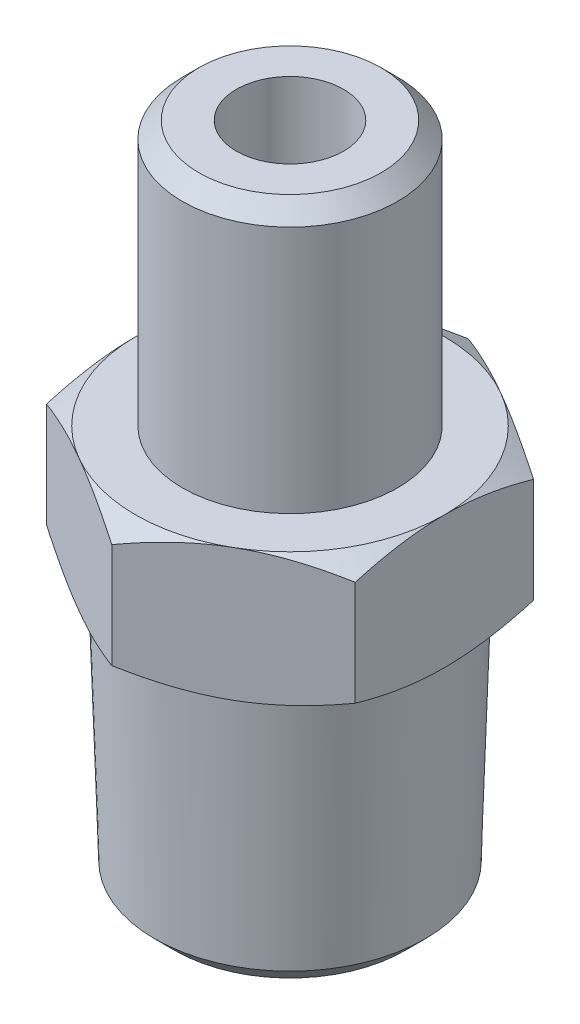
SolidWorks part; units mm, degrees
ref_plane "Front Plane" through (0, 0, 0) normal (0, 0, 1) x (1, 0, 0)
ref_plane "Top Plane" through (0, 0, 0) normal (0, 1, 0) x (1, 0, 0)
ref_plane "Right Plane" through (0, 0, 0) normal (1, 0, 0) x (0, 0, -1)
sketch "Sketch1" plane through (0, 0, 0) normal (0, 0, 1) x (1, 0, 0)
  line L0 (0, 0) -> (0, 23.8125) construction
  point P3 (0, 14.2875)
  point P4 (0, 9.525)
  dimension "Overall Length" = 23.8125
  dimension "Outlet Length" = 9.525
  dimension "Inlet Length" = 9.525
sketch "Sketch6" plane through (0, 0, 0) normal (0, 1, 0) x (1, 0, 0)
  line L1 (5.5562, -3.2079) -> (5.5562, 3.2079)
  line L2 (5.5562, 3.2079) -> (0, 6.4158)
  line L3 (0, 6.4158) -> (-5.5563, 3.2079)
  line L4 (-5.5563, 3.2079) -> (-5.5563, -3.2079)
  line L5 (-5.5563, -3.2079) -> (0, -6.4158)
  line L6 (0, -6.4158) -> (5.5562, -3.2079)
  circle A0 centre (0, 0) radius 5.5562 construction
  circle A1 centre (0, 0) radius 5.1435
  circle A2 centre (0, 0) radius 3.8735
ref_plane "Plane1" through (0, 23.8125, 0) normal (0, 1, 0) x (1, 0, 0)
ref_plane "Plane2" through (0, 9.525, 0) normal (0, 1, 0) x (1, 0, 0)
sketch "Sketch7" plane through (0, 9.525, 0) normal (0, 1, 0) x (1, 0, 0)
  circle A0 centre (0, 0) radius 5.1435 construction
  circle A1 centre (0, 0) radius 5.1435
extrude "Boss-Extrude3" add sketch "Sketch7" against normal up to vertex (9.525 mm away) draft 1.783 up to point (0, 0, 0)
sketch "Sketch8" plane through (0, 9.525, 0) normal (0, 1, 0) x (1, 0, 0)
  line L0 (5.5562, -3.2079) -> (5.5562, 3.2079) construction
  line L1 (5.5562, 3.2079) -> (0, 6.4158) construction
  line L2 (0, 6.4158) -> (-5.5563, 3.2079) construction
  line L3 (-5.5563, 3.2079) -> (-5.5563, -3.2079) construction
  line L4 (-5.5563, -3.2079) -> (0, -6.4158) construction
  line L5 (0, -6.4158) -> (5.5562, -3.2079) construction
  line L6 (5.5562, -3.2079) -> (5.5562, 3.2079)
  line L7 (5.5562, 3.2079) -> (0, 6.4158)
  line L8 (0, 6.4158) -> (-5.5563, 3.2079)
  line L9 (-5.5563, 3.2079) -> (-5.5563, -3.2079)
  line L10 (-5.5563, -3.2079) -> (0, -6.4158)
  line L11 (0, -6.4158) -> (5.5562, -3.2079)
extrude "Boss-Extrude4" add sketch "Sketch8" along normal up to vertex (4.7625 mm away) up to point (0, 14.2875, 0)
sketch "Sketch9" plane through (0, 23.8125, 0) normal (0, 1, 0) x (1, 0, 0)
  circle A0 centre (0, 0) radius 3.8735 construction
  circle A1 centre (0, 0) radius 3.8735
extrude "Boss-Extrude5" add sketch "Sketch9" against normal up to vertex (9.525 mm away) up to point (0, 14.2875, 0)
ref_plane "Plane3" through (0, 11.9062, 0) normal (0, 1, 0) x (1, 0, 0)
sketch "Sketch10" plane through (0, 0, 0) normal (0, 1, 0) x (1, 0, 0)
  circle A0 centre (0, 0) radius 1.9304
  dimension "D1" = 3.8608
extrude "Cut-Extrude1" cut sketch "Sketch10" along normal through all
sketch "Sketch11" plane through (0, 9.525, 0) normal (0, 1, 0) x (1, 0, 0)
  circle A2 centre (0, 0) radius 5.5562 construction
  circle A3 centre (0, 0) radius 5.5562
extrude "Cut-Extrude2" cut sketch "Sketch11" along normal through all draft 60 flip side to cut
mirror "Mirror1" about plane through (0, 11.9062, 0) normal (0, 1, 0) of "Cut-Extrude2"
sketch "Sketch12" plane through (0, 0, 0) normal (0, 0, 1) x (1, 0, 0)
  line L2 (4.5212, 16.8148) -> (4.5212, 20.4292)
  line L3 (4.5212, 20.4292) -> (4.1656, 20.7848)
  line L4 (4.1656, 20.7848) -> (4.1656, 23.4594)
  line L5 (4.1656, 23.4594) -> (4.5212, 23.8125)
  line L6 (4.5212, 23.8125) -> (4.5212, 27.9832)
  line L7 (4.5212, 27.9832) -> (3.085, 27.9832)
  line L11 (6.1119, 23.8125) -> (-6.1119, 23.8125) construction
  line L12 (4.0259, 23.8125) -> (3.6703, 23.4594)
  line L13 (3.6703, 23.4594) -> (3.6703, 20.7848)
  line L14 (3.6703, 20.7848) -> (4.0259, 20.4292)
  line L15 (4.0259, 20.4292) -> (4.0259, 16.8148)
  line L16 (4.0259, 16.8148) -> (4.5212, 16.8148)
  line L17 (4.0259, 23.8125) -> (0, 23.8125)
  line L18 (0, 23.8125) -> (0, 30.2768)
  line L19 (0, 0) -> (0, 23.8125) construction
  arc A3 (3.085, 27.9832) -> (1.5357, 29.3742) centre (1.6358, 27.9273) ccw
  arc A4 (1.5357, 29.3742) -> (0, 30.2768) centre (0, 28.5191) ccw
  dimension "D8" = 6.9977
  dimension "D9" = 2.9007
  dimension "D12" = 3.5154
  dimension "D1" = 2.6746
  dimension "D2" = 3.6144
  dimension "D3" = 4.5212
  dimension "D4" = 1.6358
  dimension "D5" = 13.462
  dimension "D6" = 0.3556
  dimension "D7" = 4.1707
  dimension "D10" = 4.1656
  dimension "D11" = 2.3495
  dimension "D13" = 0.4953
  dimension "D14" = 0.4953
revolve "Revolve1" [suppressed] add sketch "Sketch12" angle 360 about L0
fillet "Fillet1" [suppressed] radius 0.795
sketch "Sketch13" plane through (0, 23.8125, 0) normal (0, 1, 0) x (1, 0, 0)
  line L0 (-0.127, 4.3917) -> (0.127, 4.3917)
  line L1 (0.127, 4.3917) -> (0.127, 4.6457)
  line L2 (0.127, 4.6457) -> (-0.127, 4.6457)
  line L3 (-0.127, 4.6457) -> (-0.127, 4.3917)
  point P3 (0, 4.3917)
  dimension "D1" = 4.3917
  dimension "D2" = 0.254
  dimension "D3" = 0.254
extrude "Cut-Extrude3" [suppressed] cut sketch "Sketch13" along normal through all
pattern_circular "CirPattern1" [suppressed] count 40 over 360 about axis through (0, 0, 0) along (0, 1, 0) reverse direction yes of bodies 113
chamfer "Chamfer1" distance 0.7056 angle 45 1 edges at (0, 0, 4.8469) first distance on face at (0, 0, 1.9304)
chamfer "Chamfer2" distance 0.5953 angle 45 1 edges at (0, 23.8125, 3.8735)
move or copy body "Body-Move/Copy1" [suppressed]
sketch "Sketch15" plane through (0, 0, 0) normal (0, -1, 0) x (1, 0, 0)
  circle A0 centre (0, 0) radius 4.8469 construction
  circle A1 centre (0, 0) radius 4.8469
split "Split1" [suppressed] bodies to split 126 111
curve "Helix/Spiral1" [suppressed] parameters "NPT Thread Engagement"=10.9077, "NPT Pitch"=0.9407
sketch "Sketch16" plane through (0, 0, 0) normal (1, 0, 0) x (0, 0, -1)
  line L0 (-4.8979, -0.9113) -> (-4.8979, 0.0294) construction
  line L1 (-4.8979, -0.9113) -> (-4.0832, -0.441) construction
  line L2 (-4.0832, -0.441) -> (-4.8979, 0.0294) construction
  line L3 (-4.8979, -0.441) -> (-4.796, -0.441) construction
  line L4 (-4.0832, -0.441) -> (-4.185, -0.441) construction
  line L5 (-4.185, -0.4998) -> (-4.185, -0.3822) construction
  line L6 (-4.796, -0.8525) -> (-4.796, -0.0294) construction
  line L7 (-4.8469, -0.8819) -> (-4.8469, 0) construction
  line L8 (-5.1435, 9.525) -> (-4.8696, 0.7282) construction
  line L10 (-4.8469, 0) -> (4.8469, 0) construction
  line L11 (-4.8979, 0.0294) -> (-4.8469, -0.8819)
  line L12 (-4.8469, -0.8819) -> (-4.185, -0.4998)
  line L13 (-4.185, -0.4998) -> (-4.185, -0.3822)
  line L14 (-4.185, -0.3822) -> (-4.8979, 0.0294)
  point P13 (-4.8469, -0.441)
  dimension "D8" = 0.9407
  dimension "D2" = 0.1176
sweep "Cut-Sweep1" [suppressed] cut profiles "Sketch16" path "Helix/Spiral1"
sketch "Sketch18" plane through (0, 23.8125, 0) normal (0, 1, 0) x (1, 0, 0)
  circle A0 centre (0, 0) radius 3.8735 construction
  circle A1 centre (0, 0) radius 3.8735
curve "Helix/Spiral3" [suppressed] pitch 0.7937 height 10.3314 turns 13.016 parameters "Outlet Pitch"=0.7937
sketch "Sketch19" plane through (0, 0, 0) normal (1, 0, 0) x (0, 0, -1)
  line L0 (-3.9165, 23.7877) -> (-3.9165, 24.5814) construction
  line L1 (-3.9165, 23.7877) -> (-3.2291, 24.1846) construction
  line L2 (-3.2291, 24.1846) -> (-3.9165, 24.5814) construction
  line L3 (-3.9165, 24.1846) -> (-3.8305, 24.1846) construction
  line L4 (-3.2291, 24.1846) -> (-3.315, 24.1846) construction
  line L5 (-3.315, 24.135) -> (-3.315, 24.2342) construction
  line L6 (-3.8305, 23.8373) -> (-3.8305, 24.5318) construction
  line L7 (-3.8735, 23.8125) -> (-3.8735, 24.5566) construction
  line L8 (3.8735, 23.8125) -> (-3.8735, 23.8125) construction
  line L9 (-3.8735, 23.2172) -> (-3.8735, 14.2875) construction
  line L11 (-3.8735, 24.5566) -> (-3.8735, 23.8125)
  line L12 (-3.8735, 23.8125) -> (-3.315, 24.135)
  line L13 (-3.315, 24.135) -> (-3.315, 24.2342)
  line L14 (-3.315, 24.2342) -> (-3.8735, 24.5566)
  point P12 (-3.8735, 24.1846)
  dimension "D1" = 0.7937
  dimension "D2" = 0.0992
sweep "Cut-Sweep2" [suppressed] cut profiles "Sketch19" path "Helix/Spiral3"
sketch "Sketch20" plane through (0, 23.8125, 0) normal (0, 1, 0) x (1, 0, 0)
  circle A0 centre (0, 0) radius 3.8735
  dimension "D1" = 7.747
extrude "Boss-Extrude6" [suppressed] add sketch "Sketch20" against normal up to surface (0.061 mm away) from offset 9.586 offset against normal yes
combine bodies "Combine1" [suppressed] operation type add bodies to combine 116 119 123
ref_plane "Contact Plane 1" through (0, 0, 0) normal (0, -1, 0) x (-1, 0, 0)
ref_axis "Center Axis 1" through (0, 14.2265, 0) along (0, -1, 0)
equation "\"D2@Sketch16\" = \"D8@Sketch16\" / 8"
equation "\"D2@Sketch19\"=\"D1@Sketch19\"/8"
equation "\"D8@Sketch16\" = \"NPT Pitch@Helix/Spiral1\""
equation "\"D1@Sketch19\"=\"Outlet Pitch@Helix/Spiral3\""
equation "\"D1@Chamfer1\"=\"NPT Pitch@Helix/Spiral1\"*.75"
equation "\"D1@Chamfer2\"=\"Outlet Pitch@Helix/Spiral3\"*.75"
equation "\"D1@Sketch20\"=\"Outlet OD@Sketch6\""
